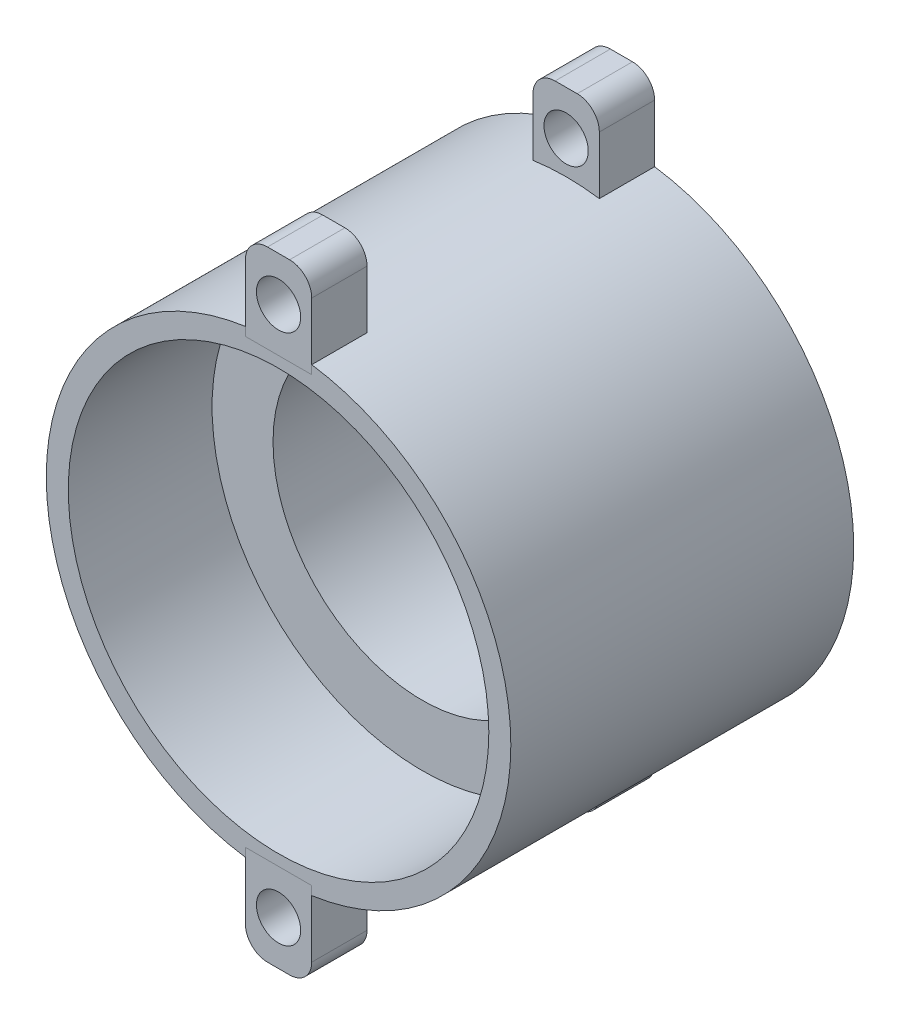
SolidWorks part; units mm, degrees
ref_plane "Front Plane" through (0, 0, 0) normal (0, 0, 1) x (1, 0, 0)
ref_plane "Top Plane" through (0, 0, 0) normal (0, 1, 0) x (1, 0, 0)
ref_plane "Right Plane" through (0, 0, 0) normal (1, 0, 0) x (0, 0, -1)
sketch "Sketch1" plane through (0, 0, 0) normal (0, 0, 1) x (1, 0, 0)
  circle A0 centre (0, 0) radius 13.5
  circle A1 centre (0, 0) radius 19.01
extrude "Boss-Extrude1" add sketch "Sketch1" along normal blind 18
sketch "Sketch2" plane through (0, 0, 18) normal (0, 0, 1) x (1, 0, 0)
  circle A0 centre (0, 0) radius 21
  circle A1 centre (0, 0) radius 19.01
extrude "Boss-Extrude2" add sketch "Sketch2" along normal blind 13 and the other way blind 18
sketch "Sketch3" plane through (0, 0, 0) normal (0, 0, -1) x (-1, 0, 0)
  line L0 (12.8914, 5.46) -> (17.4939, 7.4137)
  line L1 (15.5403, 12.0162) -> (10.9378, 10.0625)
  line L2 (15.5403, 12.0162) -> (19.4476, 2.8111)
  line L3 (19.4476, 2.8111) -> (14.8451, 0.8575)
  line L4 (10.9378, 10.0625) -> (14.8451, 0.8575)
  point P2 (12.8914, 5.46)
  point P6 (17.4939, 7.4137)
  dimension "D1" = 14
  dimension "D2" = 5.46
extrude "Cut-Extrude1" cut sketch "Sketch3" against normal offset from surface (16 mm away) 2 contours L1 L4 L3 L2 up to face at (19.01, 0, 18)
mirror "Mirror1" about plane through (0, 0, 0) normal (0, 1, 0) of "Cut-Extrude1"
mirror "Mirror2" about plane through (0, 0, 0) normal (1, 0, 0) of "Mirror1"
sketch "Sketch4" plane through (0, 0, 0) normal (0, 0, -1) x (-1, 0, 0)
  line L1 (-3, 28) -> (3, 28)
  line L2 (-3, 28) -> (-3, 20)
  line L3 (-3, 20) -> (3, 20)
  line L4 (3, 28) -> (3, 20)
  circle A0 centre (0, 24) radius 2
  point P4 (0, 20)
  dimension "D1" = 4
  dimension "D2" = 20
extrude "Boss-Extrude3" add sketch "Sketch4" along normal blind 0.0001 and the other way blind 5
fillet "Fillet1" radius 2 2 edges at (3, 28, 2.5) (-3, 28, 2.5)
mirror "Mirror5" about plane through (0, 0, 0) normal (0, 1, 0) of "Fillet1", "Boss-Extrude3"
sketch "Sketch7" plane through (0, 0, 31) normal (0, 0, 1) x (1, 0, 0)
  line L1 (-3, 28) -> (3, 28)
  line L2 (-3, 28) -> (-3, 20)
  line L3 (-3, 20) -> (3, 20)
  line L4 (3, 28) -> (3, 20)
  circle A0 centre (0, 24) radius 2
  point P4 (0, 20)
  dimension "D1" = 20
  dimension "D2" = 4
extrude "Boss-Extrude6" add sketch "Sketch7" along normal blind 0.0001 and the other way blind 5
mirror "Mirror6" about plane through (0, 0, 0) normal (0, 1, 0) of "Boss-Extrude6"
fillet "Fillet2" radius 2 4 edges at (-3, 28, 28.5) (3, 28, 28.5) (3, -28, 28.5) (-3, -28, 28.5)
